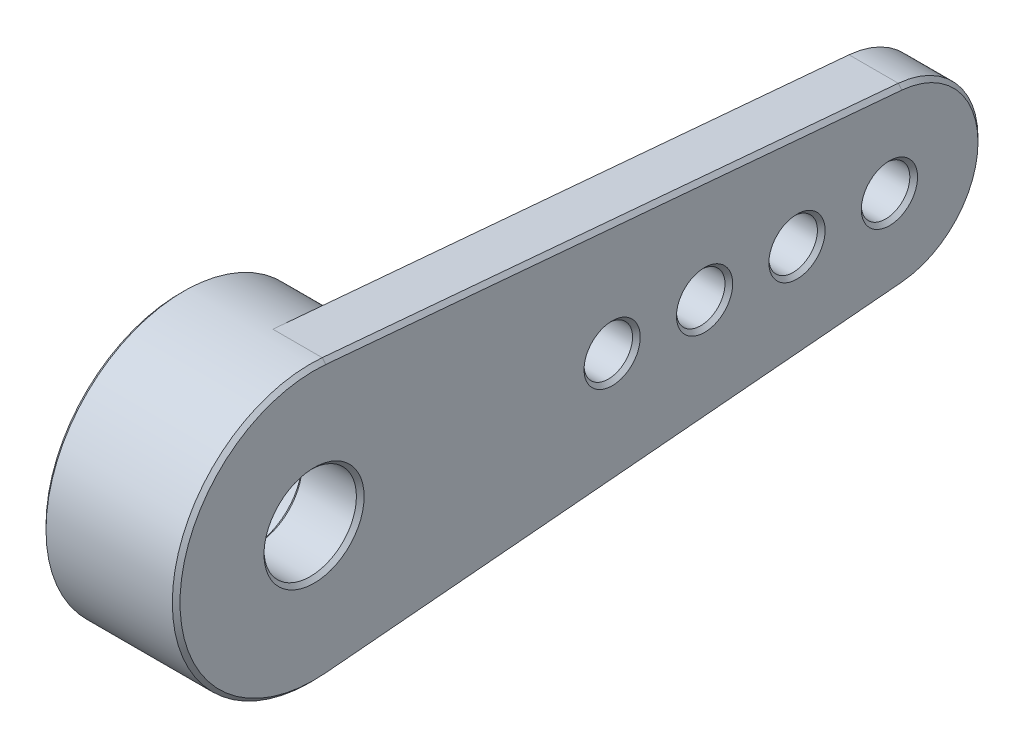
SolidWorks part; units mm, degrees
ref_plane "Front Plane" through (0, 0, 0) normal (0, 0, 1) x (1, 0, 0)
ref_plane "Top Plane" through (0, 0, 0) normal (0, 1, 0) x (1, 0, 0)
ref_plane "Right Plane" through (0, 0, 0) normal (1, 0, 0) x (0, 0, -1)
sketch "Sketch1" plane through (0, 0, 0) normal (1, 0, 0) x (0, 0, -1)
  line L0 (0, -5.3086) -> (0, 5.3086) construction
  line L1 (28.0924, -3.3356) -> (28.0924, 3.3356) construction
  line L2 (24.7695, 3.6263) -> (5.7713, 5.2884)
  line L3 (24.7695, -3.6263) -> (5.7713, -5.2884)
  line L4 (-3.2673, 0) -> (38.3183, 0) construction
  line L6 (0, -10.9604) -> (0, 17.3539) construction
  line L8 (28.0924, -10.9604) -> (28.0924, 17.3539) construction
  line L9 (5.3086, -5.3086) -> (5.3086, 5.3086) construction
  arc A0 (5.7713, 5.2884) -> (5.7713, -5.2884) centre (5.3086, 0) ccw
  arc A1 (24.7695, -3.6263) -> (24.7695, 3.6263) centre (24.4523, 0) ccw
  dimension "D2" = 10.6172
  dimension "D3" = 5
  dimension "D5" = 5
  dimension "D1" = 28.0924
  dimension "D4" = 5.3086
extrude "Boss-Extrude1" add sketch "Sketch1" along normal blind 2.9972
sketch "Sketch4" plane through (2.9972, 0, 0) normal (1, 0, 0) x (0, 0, -1)
  line L0 (24.7695, 3.6263) -> (5.7713, 5.2884) construction
  line L1 (5.7713, -5.2884) -> (24.7695, -3.6263) construction
  line L2 (24.7695, 3.6263) -> (5.7713, 5.2884) construction
  line L3 (5.7713, -5.2884) -> (24.7695, -3.6263) construction
  line L4 (24.7031, 2.8672) -> (5.7049, 4.5293)
  line L5 (5.7049, -4.5293) -> (24.7031, -2.8672)
  arc A0 (5.7713, 5.2884) -> (5.7713, -5.2884) centre (5.3086, 0) ccw construction
  arc A1 (24.7695, -3.6263) -> (24.7695, 3.6263) centre (24.4523, 0) ccw construction
  arc A2 (5.7713, 5.2884) -> (5.7713, -5.2884) centre (5.3086, 0) ccw construction
  arc A3 (24.7695, -3.6263) -> (24.7695, 3.6263) centre (24.4523, 0) ccw construction
  arc A4 (5.7049, 4.5293) -> (5.7049, -4.5293) centre (5.3086, 0) ccw
  arc A5 (24.7031, -2.8672) -> (24.7031, 2.8672) centre (24.4523, 0) ccw
  dimension "D1" = 0.762
extrude "Cut-Extrude1" cut sketch "Sketch4" against normal blind 1.524
sketch "Sketch6" plane through (1.4732, 0, 0) normal (1, 0, 0) x (0, 0, -1)
  line L0 (-1.2213, 0) -> (32.579, 0) construction
  line L1 (28.0924, 0) -> (28.0924, 4.7193) construction
  line L2 (22.352, 0) -> (22.352, 4.7193) construction
  line L3 (21.2344, 0) -> (21.2344, 4.7193) construction
  arc A0 (24.7695, -3.6263) -> (24.7695, 3.6263) centre (24.4523, 0) ccw construction
  circle A1 centre (21.2344, 0) radius 1.1176
  dimension "D3" = 2.2352
  dimension "D1" = 5.7404
  dimension "D2" = 1.1176
extrude "Cut-Extrude3" cut sketch "Sketch6" against normal through all
sketch "Sketch7" plane through (2.9972, 0, 0) normal (1, 0, 0) x (0, 0, -1)
  line L0 (24.7031, 2.8672) -> (5.7049, 4.5293) construction
  line L1 (24.7031, 2.8672) -> (5.7049, 4.5293)
  line L2 (5.7713, -5.2884) -> (24.7695, -3.6263)
  line L3 (24.7695, 3.6263) -> (5.7713, 5.2884)
  line L4 (5.7713, -5.2884) -> (24.7695, -3.6263)
  line L5 (24.7695, 3.6263) -> (5.7713, 5.2884)
  line L6 (5.7049, -4.5293) -> (24.7031, -2.8672) construction
  line L7 (5.7049, -4.5293) -> (24.7031, -2.8672)
  arc A0 (5.7049, 4.5293) -> (5.7049, -4.5293) centre (5.3086, 0) ccw construction
  arc A1 (24.7031, -2.8672) -> (24.7031, 2.8672) centre (24.4523, 0) ccw construction
  arc A2 (5.7713, 5.2884) -> (5.7713, -5.2884) centre (5.3086, 0) ccw
  arc A3 (24.7695, -3.6263) -> (24.7695, 3.6263) centre (24.4523, 0) ccw
  arc A4 (5.7713, 5.2884) -> (5.7713, -5.2884) centre (5.3086, 0) ccw
  arc A5 (24.7695, -3.6263) -> (24.7695, 3.6263) centre (24.4523, 0) ccw
  arc A6 (5.7049, 4.5293) -> (5.7049, -4.5293) centre (5.3086, 0) ccw
  arc A7 (24.7031, -2.8672) -> (24.7031, 2.8672) centre (24.4523, 0) ccw
  dimension "D1" = 0
extrude "Cut-Extrude4" cut sketch "Sketch7" against normal blind 7.62
sketch "Sketch9" plane through (1.4732, 0, 0) normal (1, 0, 0) x (0, 0, -1)
  line L2 (24.7031, 2.8672) -> (5.7049, 4.5293)
  line L3 (5.7049, -4.5293) -> (24.7031, -2.8672)
  line L4 (24.7031, 2.8672) -> (5.7049, 4.5293)
  line L5 (5.7049, -4.5293) -> (24.7031, -2.8672)
  circle A0 centre (21.2344, 0) radius 1.1176 construction
  circle A1 centre (21.2344, 0) radius 1.1176
  arc A2 (24.7031, -2.8672) -> (24.7031, 2.8672) centre (24.4523, 0) ccw
  arc A3 (5.7049, 4.5293) -> (5.7049, -4.5293) centre (5.3086, 0) ccw
  arc A4 (24.7031, -2.8672) -> (24.7031, 2.8672) centre (24.4523, 0) ccw
  arc A5 (5.7049, 4.5293) -> (5.7049, -4.5293) centre (5.3086, 0) ccw
  dimension "D1" = 0
extrude "Boss-Extrude2" add sketch "Sketch9" along normal blind 0.4064
sketch "Sketch10" plane through (1.8796, 0, 0) normal (1, 0, 0) x (0, 0, -1)
  circle A0 centre (21.2344, 0) radius 0.8001
  circle A1 centre (21.2344, 0) radius 1.1176 construction
  circle A2 centre (21.2344, 0) radius 1.1176
  dimension "D1" = 1.6002
extrude "Boss-Extrude3" add sketch "Sketch10" against normal up to surface (1.8796 mm away) up to face at (0, 0, -22.352)
sketch "Sketch11" plane through (0, 0, 0) normal (-1, 0, 0) x (0, 0, 1)
  circle A0 centre (-5.3086, 0) radius 4.5466
extrude "Boss-Extrude4" add sketch "Sketch11" along normal blind 2.54
sketch "Sketch12" plane through (-2.54, 0, 0) normal (-1, 0, 0) x (0, 0, 1)
  circle A0 centre (-5.3086, 0) radius 2.8702
  dimension "D1" = 5.7404
extrude "Cut-Extrude5" cut sketch "Sketch12" against normal blind 2.3749
sketch "Sketch13" plane through (-0.1651, 0, 0) normal (-1, 0, 0) x (0, 0, 1)
  circle A0 centre (-5.3086, 0) radius 1.524
  dimension "D1" = 3.048
extrude "Cut-Extrude6" cut sketch "Sketch13" against normal through all
sketch "Sketch14" plane through (1.8796, 0, 0) normal (1, 0, 0) x (0, 0, -1)
  circle A0 centre (18.1864, 0) radius 0.8001
  circle A1 centre (15.1384, 0) radius 0.8001
  circle A2 centre (24.2824, 0) radius 0.8001
  circle A3 centre (21.2344, 0) radius 0.8001 construction
  circle A4 centre (21.2344, 0) radius 0.8001 construction
  dimension "D1" = 3.048
  dimension "D2" = 3.048
  dimension "D3" = 3.048
extrude "Cut-Extrude7" cut sketch "Sketch14" against normal through all
chamfer "Chamfer1" distance 0.127 angle 45 4 edges at (-2.54, 0, -0.762) (-2.54, 0, -2.4384) (-0.1651, 0, -3.7846) (1.8796, 0, -6.8326)
chamfer "Chamfer2" distance 0.127 angle 45 12 edges at (0, 0, -15.9385) (1.8796, 0, -15.9385) (0, 0, -18.9865) (1.8796, 0, -18.9865) (1.8796, 0, -22.0345) (0, 0, -22.0345) (0, 0, -25.0825) (1.8796, 0, -25.0825) (1.8796, 0, -27.3304) (1.8796, -3.6982, -15.204) (1.8796, 0, -0.762) (1.8796, 3.6982, -15.204)
chamfer "Chamfer3" distance 0.127 angle 45 3 edges at (0, 0, -27.3304)
scale "Scale1" scale about centroid uniform scaling yes scale factor 0.6
